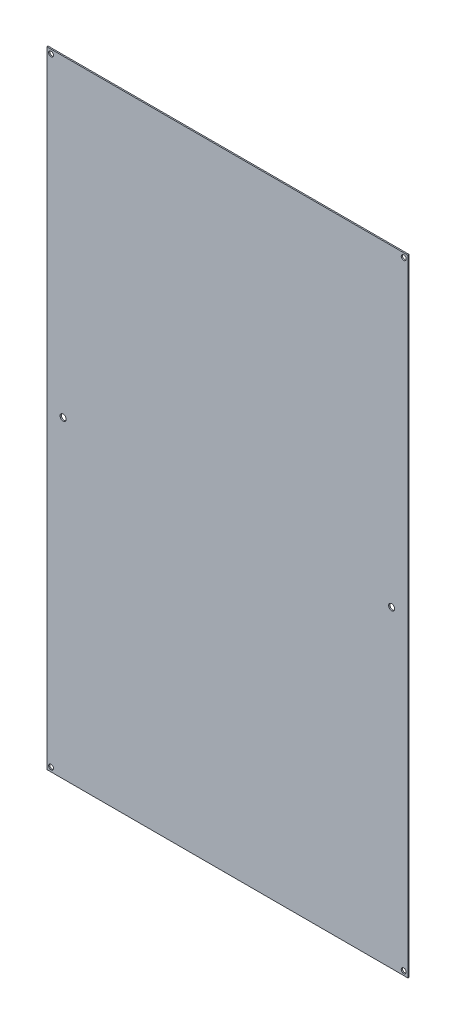
SolidWorks part; units mm, degrees
ref_plane "Front Plane" through (0, 0, 0) normal (0, 0, 1) x (1, 0, 0)
ref_plane "Top Plane" through (0, 0, 0) normal (0, 1, 0) x (1, 0, 0)
ref_plane "Right Plane" through (0, 0, 0) normal (1, 0, 0) x (0, 0, -1)
sketch "Sketch1" plane through (0, 0, 0) normal (0, 0, 1) x (1, 0, 0)
  line L1 (-109.8476, 958.0814) -> (-109.8476, 108.0814) construction
  line L2 (360.1524, 958.0814) -> (360.1524, 108.0814) construction
  line L3 (360.1524, 919.9815) -> (-109.8476, 919.9815) construction
  line L4 (-109.8476, 108.0814) -> (360.1524, 108.0814) construction
  line L5 (-109.8476, 919.9815) -> (-109.8476, 108.0814) construction
  line L6 (360.1524, 919.9815) -> (360.1524, 108.0814) construction
  line L7 (360.1524, 919.9815) -> (-109.8476, 919.9815) construction
  line L8 (-107.8476, 110.0814) -> (358.1524, 110.0814)
  line L9 (358.1524, 917.9815) -> (358.1524, 110.0814)
  line L10 (358.1524, 917.9815) -> (-107.8476, 917.9815)
  line L11 (-107.8476, 917.9815) -> (-107.8476, 110.0814)
  circle A0 centre (-102.4054, 115.5224) radius 3.175 construction
  circle A1 centre (352.7102, 115.5224) radius 3.175 construction
  circle A2 centre (-102.4054, 912.5404) radius 3.175 construction
  circle A3 centre (352.7102, 912.5404) radius 3.175 construction
  circle A4 centre (-102.4054, 115.5224) radius 3.175
  circle A5 centre (352.7102, 115.5224) radius 3.175
  circle A6 centre (-102.4054, 912.5404) radius 3.175
  circle A7 centre (352.7102, 912.5404) radius 3.175
  circle A8 centre (-86.8936, 514.0314) radius 3.9687 construction
  circle A9 centre (337.1984, 514.0314) radius 3.9688 construction
  circle A10 centre (-86.8936, 514.0314) radius 3.9687
  circle A11 centre (337.1984, 514.0314) radius 3.9688
  dimension "\"Panel_Offset\"" = 2
extrude "Boss-Extrude1" add sketch "Sketch1" along normal blind 1.6002
